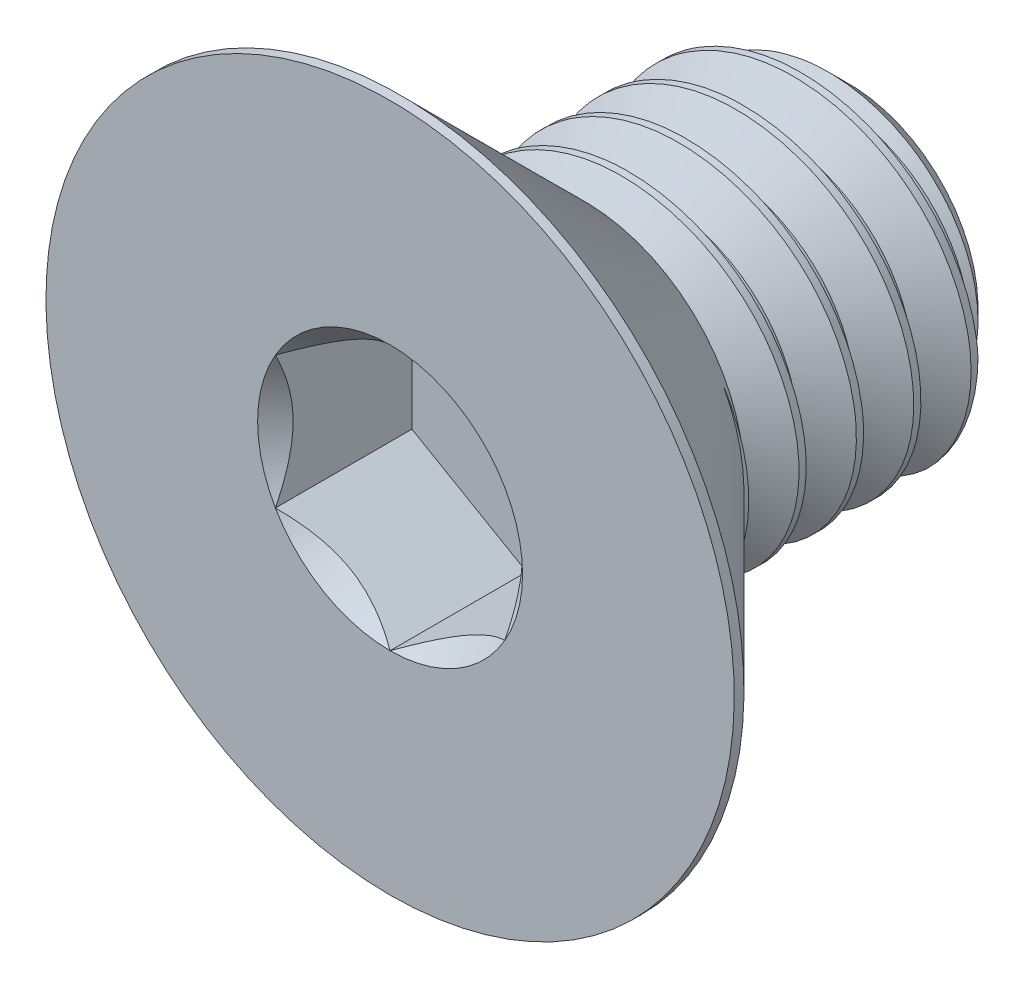
SolidWorks part; units mm, degrees
ref_plane "Front" through (0, 0, 0) normal (0, 0, 1) x (1, 0, 0)
ref_plane "Top" through (0, 0, 0) normal (0, 1, 0) x (1, 0, 0)
ref_plane "Right" through (0, 0, 0) normal (1, 0, 0) x (0, 0, -1)
sketch "Sketch11" plane through (0, 0, 0) normal (1, 0, 0) x (0, 0, -1)
  line L0 (-2, 3) -> (2, 3) construction
  line L5 (-2, 3) -> (-2, -3) construction
  line L6 (2, 1.5) -> (2, -1.5) construction
  line L7 (-1.99, 1) -> (-1.99, -1) construction
  line L8 (1.9688, 1.5541) -> (2.4688, 1.5541) construction
  line L9 (2.4688, 1.5541) -> (2.2188, 1.1211) construction
  line L10 (2.2188, 1.1211) -> (1.9688, 1.5541) construction
  line L11 (2.1875, 1.1752) -> (2.25, 1.1752) construction
  line L12 (2.2188, 1.1752) -> (2.2188, 1.1211) construction
  line L13 (1.9844, 1.5271) -> (2.4531, 1.5271) construction
  line L14 (2.2188, 1.5541) -> (2.2188, 1.5) construction
  line L15 (2, 1.5) -> (2.4375, 1.5) construction
  line L17 (-1.915, 3) -> (1.085, 0) construction
  line L18 (1.085, 0) -> (-1.915, -3) construction
  point P3 (-0.3, 3)
  point P8 (0, 3)
  point P21 (2.2188, 1.5271)
  point P26 (-2, 0)
  point P28 (-1.99, 0)
  point P29 (2, 0)
  dimension "Length" = 4
  dimension "Head Diameter" = 6
  dimension "Thread Major Diameter" = 3
  dimension "Head Height" = 1.7
  dimension "Drive Size" = 2
  dimension "Thread Pitch" = 0.5
  dimension "D1" = 0.0625
  dimension "D2" = 0.01
  dimension "D3" = 0.085
  dimension "Countersink Angle" = 90
sketch "Sketch1" plane through (0, 0, 0) normal (1, 0, 0) x (0, 0, -1)
  line L2 (-0.3, 1.5) -> (2, 1.5)
  line L3 (2, 1.5) -> (2, 0)
  line L4 (-0.81, 1.5) -> (-0.81, 0)
  line L5 (-0.3, 1.5) -> (-0.81, 1.5)
  line L6 (-2, 3) -> (-2, -3) construction
  line L7 (2, 1.5) -> (2, -1.5) construction
  line L8 (-0.81, 0) -> (2, 0)
  dimension "D1" = 1.19
revolve "Revolve1" add sketch "Sketch1" angle 360 mid plane about L8
chamfer "Chamfer1" distance 0.375 angle 45 1 edges at (0, -1.5, -2)
sketch "Sketch7" plane through (0, 0, 0) normal (1, 0, 0) x (0, 0, -1)
  line L2 (-2, 3) -> (-1.915, 3)
  line L5 (-0.3, 1.385) -> (-0.3, 0)
  line L6 (-2, 3) -> (-2, 0)
  line L8 (-2, 3) -> (-2, -3) construction
  line L9 (-2, 0) -> (-0.3, 0)
  line L12 (-1.915, 3) -> (-0.3, 1.385)
  line L13 (-1.915, 3) -> (1.085, 0) construction
revolve "Revolve2" add sketch "Sketch7" angle 360 mid plane about L9 region at (0, 1.1696, 1.2571)
ref_plane "Plane1" through (0, 0, 0.3) normal (0, 0, 1) x (1, 0, 0)
sketch "Sketch5" plane through (0, 0, 2) normal (0, 0, 1) x (1, 0, 0)
  line L1 (1, -0.5774) -> (1, 0.5774)
  line L2 (1, 0.5774) -> (0, 1.1547)
  line L3 (0, 1.1547) -> (-1, 0.5774)
  line L4 (-1, 0.5774) -> (-1, -0.5774)
  line L5 (-1, -0.5774) -> (0, -1.1547)
  line L6 (0, -1.1547) -> (1, -0.5774)
  circle A0 centre (0, 0) radius 1 construction
extrude "Cut-Extrude2" cut sketch "Sketch5" against normal blind 1.19
sketch "Sketch6" plane through (0, 0, 2) normal (0, 0, -1) x (-1, 0, 0)
  circle A0 centre (0, 0) radius 1.1547
extrude "Cut-Extrude3" cut sketch "Sketch6" along normal blind 1.19 draft 45
sketch "Sketch12" plane through (0, 0, -2) normal (0, 0, -1) x (-1, 0, 0)
  circle A0 centre (0, 0) radius 1.5 construction
  circle A1 centre (0, 0) radius 1.5
curve "Helix/Spiral1" pitch 0.5 height 4 radius 1.5 centre (0, 0, -2) axis (0, 0, 1) start towards (0, 1, 0)
sketch "Sketch13" plane through (0, 0, 0) normal (1, 0, 0) x (0, 0, -1)
  line L0 (1.9844, 1.5271) -> (2.4531, 1.5271)
  line L1 (2.4531, 1.5271) -> (2.25, 1.1752)
  line L2 (2.25, 1.1752) -> (2.1875, 1.1752)
  line L3 (2.1875, 1.1752) -> (1.9844, 1.5271)
sweep "Cut-Sweep1" cut profiles "Sketch13" path "Helix/Spiral1" align with end faces yes
combine bodies "Combine1" operation type add bodies to combine 113 127
equation "\"D1@Chamfer1\"=\"Thread Pitch@Sketch11\" * .75"
equation "\"D1@Cut-Extrude2\"= \"Head Height@Sketch11\" * .7"
equation "\"D1@Cut-Extrude3\" = \"D1@Cut-Extrude2\""
equation "\"D1@Sketch11\"=\"Thread Pitch@Sketch11\"/8"
equation "\"D3@Sketch11\"=\"Head Height@Sketch11\"*.05"
equation "\"D4@Helix/Spiral1\"=\"Thread Pitch@Sketch11\""
equation "\"D1@Sketch1\"=\"Head Height@Sketch11\"*.7"
equation "\"D3@Helix/Spiral1\"=\"Length@Sketch11\""
